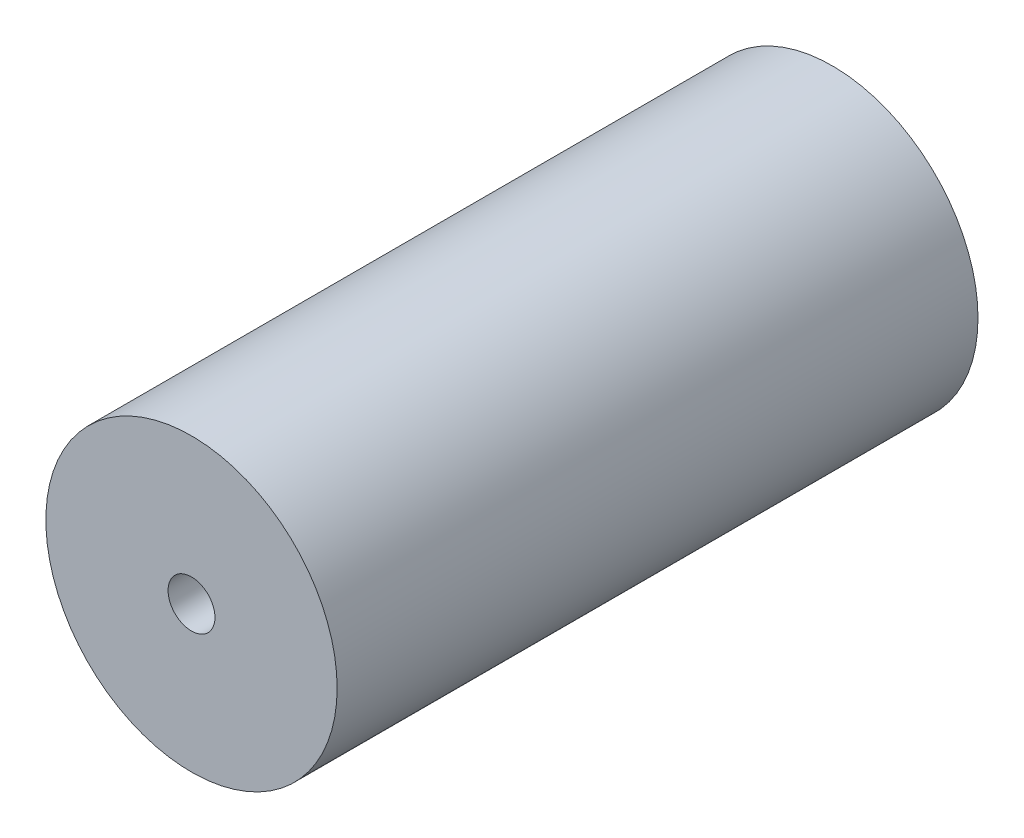
SolidWorks part; units mm, degrees
ref_plane "Ebene vorne" through (0, 0, 0) normal (0, 0, 1) x (1, 0, 0)
ref_plane "Ebene oben" through (0, 0, 0) normal (0, 1, 0) x (1, 0, 0)
ref_plane "Ebene rechts" through (0, 0, 0) normal (1, 0, 0) x (0, 0, -1)
sketch "Skizze1" plane through (0, 0, 0) normal (0, 0, 1) x (1, 0, 0)
  circle A0 centre (0, 0) radius 25
  circle A1 centre (0, 0) radius 4.025
  dimension "D1" = 50
  dimension "D2" = 8.05
extrude "Aufsatz-Linear austragen1" add sketch "Skizze1" along normal blind 110
ref_axis "Achse1" through (0, 0, 110) along (0, 0, -1)
